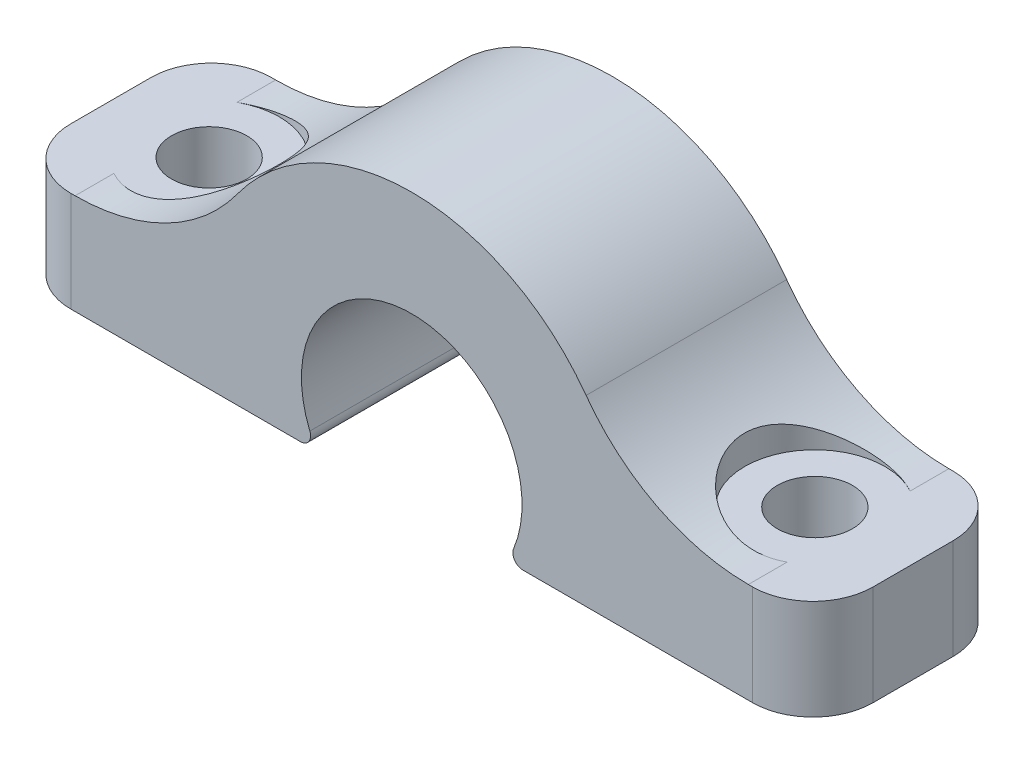
SolidWorks part; units mm, degrees
ref_plane "Front Plane" through (0, 0, 0) normal (0, 0, 1) x (1, 0, 0)
ref_plane "Top Plane" through (0, 0, 0) normal (0, 1, 0) x (1, 0, 0)
ref_plane "Right Plane" through (0, 0, 0) normal (1, 0, 0) x (0, 0, -1)
sketch "Sketch1" plane through (0, 0, 0) normal (0, 1, 0) x (1, 0, 0)
  line L1 (-20, 5) -> (20, 5)
  line L2 (-20, 5) -> (-20, -5)
  line L3 (-20, -5) -> (20, -5)
  line L4 (20, 5) -> (20, -5)
  line L5 (-20, 5) -> (20, -5) construction
  line L6 (-20, -5) -> (20, 5) construction
  point P0 (0, 0)
  dimension "D1" = 40
  dimension "D2" = 10
sketch "Sketch2" plane through (0, 0, 0) normal (0, 0, 1) x (1, 0, 0)
  line L0 (-4.7339, 0) -> (4.7339, 0) construction
  line L1 (0, -55) -> (0, 55) construction
  line L2 (-10.3789, 0) -> (10.3789, 0) construction
  line L3 (-10.3789, 0) -> (-4.7339, 0)
  line L4 (4.7339, 0) -> (10.3789, 0)
  arc A0 (-4.7339, 0) -> (4.7339, 0) centre (0, 2.8) cw
  arc A2 (-10.3789, 0) -> (10.3789, 0) centre (0, 2.8) cw
  point P3 (0, 2.8)
  point P4 (0, 0)
  point P5 (-4.7339, 0)
  point P6 (4.7339, 0)
  dimension "D4" = 10.75
  dimension "D1" = 2.8
  dimension "D2" = 5.5
  dimension "D3" = 5.5
extrude "Boss-Extrude1" add sketch "Sketch1" against normal blind 5 from offset 1 offset against normal yes
extrude "Boss-Extrude2" add sketch "Sketch2" along normal blind 5 and the other way blind 5
sketch "Sketch3" plane through (0, 0, 0) normal (0, 1, 0) x (1, 0, 0)
  line L0 (-10.75, -5) -> (10.75, -5) construction
  line L1 (-20, 5) -> (-10, 5)
  line L2 (-20, 5) -> (-20, -5)
  line L3 (-20, -5) -> (-10, -5)
  line L4 (-10, 5) -> (-10, -5)
  line L5 (0, -55) -> (0, 55) construction
  line L6 (20, -5) -> (10, -5)
  line L7 (20, 5) -> (20, -5)
  line L8 (20, 5) -> (10, 5)
  line L9 (10, 5) -> (10, -5)
  dimension "D1" = 10
extrude "Boss-Extrude3" add sketch "Sketch3" along normal blind 5
fillet "Fillet1" radius 3 4 edges at (20, 2.5, -5) (20, 2.5, 5) (-20, 2.5, -5) (-20, 2.5, 5)
fillet "Fillet2" radius 3 4 edges at (-20, -3.5, 5) (-20, -3.5, -5) (20, -3.5, 5) (20, -3.5, -5)
fillet "Fillet3" radius 0.5 2 edges at (-4.7339, 0, 0) (4.7339, 0, 0)
fillet "Fillet4" radius 10 2 edges at (10.5225, 5, 0) (-10.5225, 5, 0)
sketch "Sketch4" plane through (0, 0, 0) normal (0, 1, 0) x (1, 0, 0)
  line L0 (-10.7525, 0) -> (10.7525, 0) construction
  circle A0 centre (-15.1, 0) radius 1.875
  circle A1 centre (15.1, 0) radius 1.875
  dimension "D1" = 3.75
  dimension "D2" = 15.1
  dimension "D3" = 15.1
extrude "Cut-Extrude1" cut sketch "Sketch4" against normal through all both and the other way through all
sketch "Sketch5" plane through (0, 0, 0) normal (0, 1, 0) x (1, 0, 0)
  line L0 (0, -5.5) -> (0, 5.5) construction
  circle A0 centre (-15.1, 0) radius 3.5
  circle A1 centre (15.1, 0) radius 3.5
  dimension "D1" = 7
extrude "Cut-Extrude2" cut sketch "Sketch5" along normal blind 10 from offset 5
sketch "Sketch7" plane through (0, 0, 0) normal (0, 1, 0) x (1, 0, 0)
  line L5 (24.1582, -13.2438) -> (-27.5449, -13.2438)
  line L6 (24.1582, -13.2438) -> (24.1582, 9.8009)
  line L7 (24.1582, 9.8009) -> (-27.5449, 9.8009)
  line L8 (-27.5449, -13.2438) -> (-27.5449, 9.8009)
extrude "Cut-Extrude4" cut sketch "Sketch7" against normal through all
equation "\"shaftDiameter\"= 10mm"
equation "\"holeDiameter\"= 3.75mm"
equation "\"D1@Sketch4\"=\"holeDiameter\""
